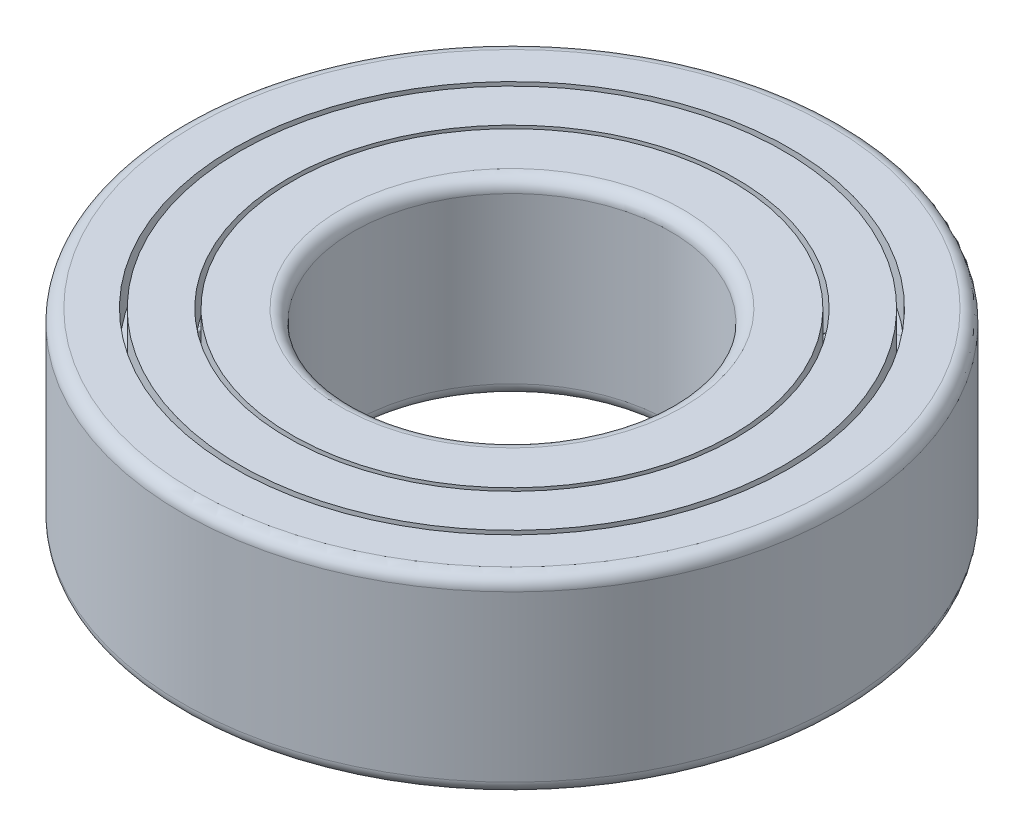
SolidWorks part; units mm, degrees
material "Plain Carbon Steel"
ref_plane "Front Plane" through (0, 0, 0) normal (0, 0, 1) x (1, 0, 0)
ref_plane "Top Plane" through (0, 0, 0) normal (0, 1, 0) x (1, 0, 0)
ref_plane "Right Plane" through (0, 0, 0) normal (1, 0, 0) x (0, 0, -1)
sketch "Sketch1" plane through (0, 0, 0) normal (0, 0, 1) x (1, 0, 0)
  line L0 (0, -7.5) -> (0, 7.5) construction
  line L1 (15.75, -4.5) -> (23.25, -4.5) construction
  line L2 (-12.5, 0) -> (12.5, 0) construction
  line L3 (-26, 7.5) -> (26, 7.5) construction
  line L7 (-26, -7.5) -> (26, -7.5) construction
  line L8 (15.75, 4.5) -> (23.25, 4.5) construction
  line L11 (15.15, -7.5) -> (15.75, -5.2608) construction
  line L12 (15.75, -5.2608) -> (15.75, -7.5) construction
  circle A0 centre (23.25, 4.5) radius 0.2502 construction
  circle A1 centre (15.75, 4.5) radius 0.2502 construction
  circle A2 centre (23.25, -4.5) radius 0.2502 construction
  point P0 (15.75, 4.5)
  point P4 (0, 0)
  point P10 (0, 0)
  point P11 (0, 7.5)
  point P13 (-15.75, 4.5)
  point P15 (15.75, -5.2608)
  point P16 (23.25, 4.5)
  point P21 (0, -7.5)
  point P22 (19.5, 4.5)
  point P23 (15.75, -4.0608)
  point P26 (17.35, 7.5)
  point P29 (21.9, 7.5)
  point P31 (19.5, -4.5)
  point P34 (15.75, -6.9)
  dimension "D3" = 0.5004
  dimension "B" = 15
  dimension "d" = 25
  dimension "(D)" = 52
  dimension "F" = 31.5
  dimension "D2" = 15
  dimension "D1" = 43.8
  dimension "E" = 46.5
  dimension "(d1)" = 34.7
  dimension "S" = 1.2
  dimension "D4" = 3
  dimension "D5" = 1.2
  dimension "D6" = 2.2392
  dimension "D7" = 9
sketch "Sketch2" plane through (0, 0, 0) normal (0, 0, 1) x (1, 0, 0)
  line L0 (15.15, -7.5) -> (15.75, -5.2608)
  line L1 (15.75, -5.2608) -> (15.75, 4.1462)
  line L2 (16.1038, 4.5) -> (17.35, 4.5)
  line L3 (15.75, 4.5) -> (23.25, 4.5) construction
  line L4 (17.35, 4.5) -> (17.35, 7.5)
  line L5 (17.35, 7.5) -> (13.5, 7.5)
  line L6 (-26, 7.5) -> (26, 7.5) construction
  line L7 (12.5, 6.5) -> (12.5, -6.5)
  line L8 (-26, -7.5) -> (26, -7.5) construction
  line L10 (0, 0) -> (0, 7.5) construction
  line L11 (15.9269, 4.6769) -> (16.1038, 4.5)
  line L12 (15.75, 4.5) -> (16.1038, 4.1462) construction
  line L13 (15.75, 4.5) -> (15.4998, 4.5) construction
  line L14 (15.5731, 4.3231) -> (15.75, 4.1462)
  line L16 (15.15, -7.5) -> (15.75, -5.2608) construction
  line L17 (15.15, -7.5) -> (13.5, -7.5)
  arc A0 (13.5, -7.5) -> (12.5, -6.5) centre (13.5, -6.5) cw
  arc A1 (12.5, 6.5) -> (13.5, 7.5) centre (13.5, 6.5) cw
  circle A2 centre (15.75, 4.5) radius 0.2502 construction
  arc A3 (15.9269, 4.6769) -> (15.5731, 4.3231) centre (15.75, 4.5) ccw
  point P24 (12.5, -7.5)
  point P27 (12.5, 7.5)
  dimension "R" = 1
  dimension "D2" = 45
revolve "Revolve3" add sketch "Sketch2" angle 360 about L10
ref_axis "Axis2" through (0, 6.5, 0) along (0, -1, 0)
sketch "Sketch5" plane through (0, 0, 0) normal (0, 0, 1) x (1, 0, 0)
  line L0 (21.9, 7.5) -> (21.9, 4.5)
  line L1 (15.75, 4.5) -> (23.25, 4.5) construction
  line L2 (21.9, 4.5) -> (22.8962, 4.5)
  line L3 (23.25, 4.1462) -> (23.25, -4.1462)
  line L4 (22.8962, -4.5) -> (21.9, -4.5)
  line L5 (15.75, -4.5) -> (23.25, -4.5) construction
  line L6 (21.9, -4.5) -> (21.9, -7.5)
  line L7 (-26, -7.5) -> (26, -7.5) construction
  line L8 (21.9, -7.5) -> (25, -7.5)
  line L9 (26, -6.5) -> (26, 6.5)
  line L10 (25, 7.5) -> (21.9, 7.5)
  line L11 (23.25, 4.5) -> (22.8962, 4.1462) construction
  line L12 (23.4269, 4.3231) -> (23.25, 4.1462)
  line L13 (23.0731, 4.6769) -> (22.8962, 4.5)
  line L14 (23.4269, -4.3231) -> (23.25, -4.1462)
  line L15 (22.8962, -4.5) -> (23.0731, -4.6769)
  line L16 (23.25, -4.5) -> (22.8962, -4.1462) construction
  line L17 (0, 0) -> (0, 7.5) construction
  arc A0 (25, -7.5) -> (26, -6.5) centre (25, -6.5) ccw
  arc A1 (25, 7.5) -> (26, 6.5) centre (25, 6.5) cw
  arc A2 (23.4269, 4.3231) -> (23.0731, 4.6769) centre (23.25, 4.5) ccw
  circle A3 centre (23.25, 4.5) radius 0.2502 construction
  arc A4 (23.0731, -4.6769) -> (23.4269, -4.3231) centre (23.25, -4.5) ccw
  circle A5 centre (23.25, -4.5) radius 0.2502 construction
  point P21 (26, -7.5)
  point P24 (26, 7.5)
  dimension "D1" = 1
  dimension "D2" = 45
  dimension "D3" = 45
revolve "Revolve4" add sketch "Sketch5" angle 360 about L17
sketch "Sketch6" plane through (0, 0, 0) normal (0, 1, 0) x (1, 0, 0)
  circle A2 centre (-19.5, 0) radius 3.75
  circle A3 centre (0, 0) radius 15.75 construction
  circle A4 centre (0, 0) radius 23.25 construction
  point P1 (-15.75, 0)
  point P8 (-23.25, 0)
extrude "Boss-Extrude4" add sketch "Sketch6" along normal mid plane 9 separate body
fillet "Fillet1" radius 0.2 2 edges at (-19.5, -4.5, 3.75) (-19.5, 4.5, 3.75)
pattern_circular "CirPattern2" count 13 over 360 about axis through (0, 6.5, 0) along (0, -1, 0) of bodies 148
sketch "Sketch9" plane through (0, -7.5, 0) normal (0, -1, 0) x (1, 0, 0)
  line L0 (-17.697, 0) -> (-21.462, 0) construction
  circle A0 centre (0, 0) radius 17.697
  circle A2 centre (0, 0) radius 21.462
  point P6 (-19.5795, 0)
  dimension "D1" = 42.924
  dimension "D2" = 35.394
extrude "Boss-Extrude7" add sketch "Sketch9" against normal up to surface (15 mm away) separate body up to face at (21.9, 7.5, 0)
sketch "Sketch10" plane through (0, -4.5, 0) normal (0, -1, 0) x (1, 0, 0)
  circle A0 centre (0, 0) radius 19.5795
  circle A1 centre (0, 0) radius 23.25
  circle A3 centre (0, 0) radius 23.25 construction
extrude "Boss-Extrude11" add sketch "Sketch10" against normal up to surface (9 mm away) separate body up to face at (-19.5, 4.5, 3.55)
ref_axis "Center Axis 1" through (0, 6.5, 0) along (0, -1, 0)
ref_plane "Contact Plane 1" through (0, 7.5, 0) normal (0, 1, 0) x (1, 0, 0)
ref_plane "Contact Plane 2" through (0, -7.5, 0) normal (0, -1, 0) x (-1, 0, 0)
equation "\"D1@Boss-Extrude4\"=\"D7@Sketch1\""
equation "\"D5@Sketch1\"=\"S@Sketch1\""
equation "\"D3@Sketch1\"=\"D7@Sketch1\"*.0556"
equation "\"D1@Sketch9\"=\"D1@Sketch1\"*.98"
equation "\"D2@Sketch9\"=\"(d1)@Sketch1\"*1.02"
